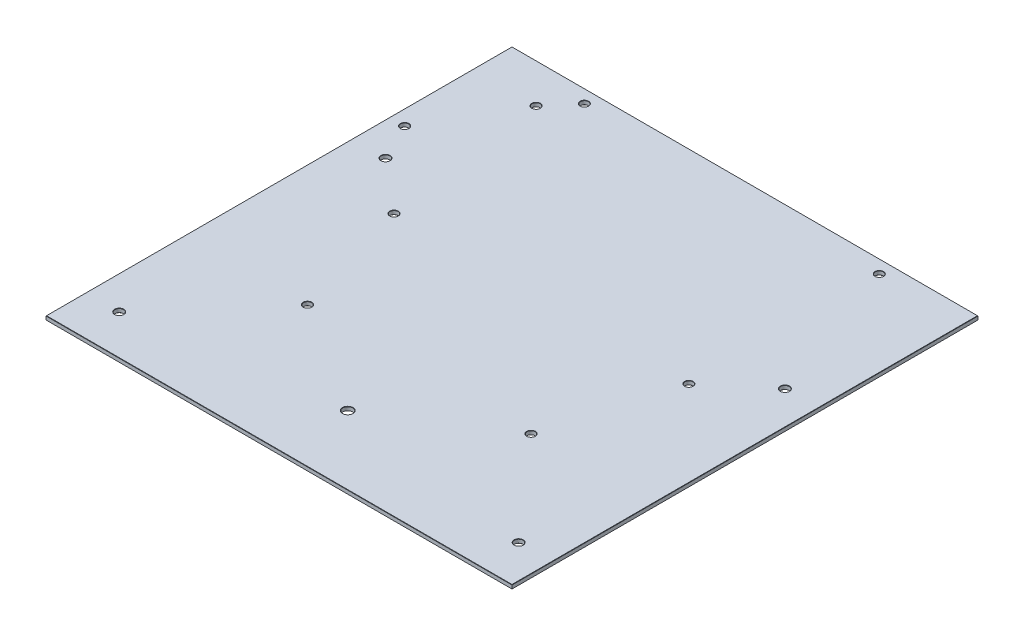
SolidWorks part; units mm, degrees
ref_plane "Front Plane" through (0, 0, 0) normal (0, 0, 1) x (1, 0, 0)
ref_plane "Top Plane" through (0, 0, 0) normal (0, 1, 0) x (1, 0, 0)
ref_plane "Right Plane" through (0, 0, 0) normal (1, 0, 0) x (0, 0, -1)
sketch "Sketch1" plane through (0, 0, 0) normal (0, 1, 0) x (1, 0, 0)
  line L1 (-175, 175) -> (175, 175)
  line L2 (-175, 175) -> (-175, -175)
  line L3 (-175, -175) -> (175, -175)
  line L4 (175, 175) -> (175, -175)
  line L5 (-175, 175) -> (175, -175) construction
  line L6 (-175, -175) -> (175, 175) construction
  point P0 (0, 0)
  dimension "D1" = 350
extrude "Boss-Extrude1" add sketch "Sketch1" along normal blind 3
sketch "Sketch6" plane through (0, 3, 0) normal (0, 1, 0) x (1, 0, 0)
  line L0 (-175, 55) -> (175, 55) construction
  line L1 (-175, 175) -> (-175, -175) construction
  line L2 (175, -175) -> (175, 175) construction
  line L3 (-150, -145) -> (-175, -145) construction
  line L4 (150, -145) -> (175, -145) construction
  line B0 (-150, -145) -> (150, -145) construction
  line B1 (150, -145) -> (150, 55) construction
  line B2 (150, 55) -> (-150, 55) construction
  line B3 (-150, 55) -> (-150, -145) construction
  line B4 (-150, -145) -> (150, 55) construction
  circle B5 centre (-150, -145) radius 3
  circle B6 centre (150, 55) radius 3
  circle B7 centre (150, -145) radius 3
  circle B8 centre (-150, 55) radius 3
sketch_block_instance "Block2-1"
sketch_block "Block2"
sketch "Sketch2" plane through (0, 3, 0) normal (0, 1, 0) x (1, 0, 0)
  line L0 (-175, 175) -> (-175, 55) construction
  line L1 (-175, 175) -> (-175, -175) construction
  line L2 (-175, 55) -> (175, 55) construction
  line L3 (175, -175) -> (175, 175) construction
  line L4 (-155, -175) -> (-155, -155) construction
  line L5 (-175, -175) -> (175, -175) construction
  line L6 (-155, -155) -> (155, -155) construction
  line L7 (155, -155) -> (155, -175) construction
  line L8 (-155, -155) -> (-155, -151.75) construction
  line L9 (155, -155) -> (155, -151.75) construction
  line L10 (155, -151.75) -> (-155, -151.75) construction
  line L11 (-151.75, 55) -> (-151.75, -151.75) construction
  line L12 (-151.75, -151.75) -> (151.75, 55) construction
  line L13 (151.75, 55) -> (151.75, -151.75) construction
  line L14 (151.75, -151.75) -> (-151.75, 55) construction
  line L15 (0, -48.375) -> (0, -123.375) construction
  circle A1 centre (-151.75, -151.75) radius 3.25 construction
  circle A2 centre (151.75, -151.75) radius 3.25 construction
  circle A3 centre (151.75, 55) radius 3.25 construction
  circle A4 centre (-151.75, 55) radius 3.25 construction
  circle A6 centre (0, -123.375) radius 3.75
  circle A7 centre (-150, 55) radius 3 construction
  circle A8 centre (150, 55) radius 3 construction
  circle A9 centre (150, -145) radius 3 construction
  circle A10 centre (-150, -145) radius 3 construction
  circle A11 centre (-150, 55) radius 3 construction
  circle A12 centre (150, 55) radius 3 construction
  circle A13 centre (150, -145) radius 3 construction
  circle A14 centre (-150, -145) radius 3 construction
  circle A15 centre (-150, -145) radius 3.25
  circle A16 centre (-150, 55) radius 3.25
  circle A17 centre (150, 55) radius 3.25
  circle A18 centre (150, -145) radius 3.25
  point P8 (-155, 55)
  point P9 (155, 55)
  dimension "D6" = 6.5
  dimension "D7" = 7.5
  dimension "D8" = 6.5
  dimension "D1" = 120
  dimension "D2" = 20
  dimension "D3" = 20
  dimension "D4" = 20
  dimension "D5" = 75
extrude "Cut-Extrude1" cut sketch "Sketch2" against normal up to surface (3 mm away) up to face at (0, 0, 0)
sketch "Sketch3" plane through (0, 3, 0) normal (0, 1, 0) x (1, 0, 0)
  circle A0 centre (-83.95, -69.6649) radius 3.05 construction
  circle A1 centre (83.95, -69.6649) radius 3.05 construction
  circle A2 centre (-83.95, -69.6649) radius 3.05
  circle A3 centre (83.95, -69.6649) radius 3.05
extrude "Cut-Extrude2" cut sketch "Sketch3" against normal up to surface (3 mm away) up to face at (150, 0, 148.25)
sketch "Sketch4" plane through (0, 3, 0) normal (0, 1, 0) x (1, 0, 0)
  circle A0 centre (-110.733, 165.1108) radius 3 construction
  circle A1 centre (-110.733, 165.1108) radius 3
  circle A2 centre (-110.75, 22.1108) radius 3 construction
  circle A3 centre (110.75, 22.0845) radius 3 construction
  circle A4 centre (110.767, 165.0845) radius 3 construction
  circle A5 centre (-110.75, 22.1108) radius 3
  circle A6 centre (110.75, 22.0845) radius 3
  circle A7 centre (110.767, 165.0845) radius 3
extrude "Cut-Extrude3" cut sketch "Sketch4" against normal up to surface (3 mm away) up to face at (-83.95, 0, 72.7149)
sketch "Sketch5" plane through (0, 3, 0) normal (0, 1, 0) x (1, 0, 0)
  circle A0 centre (-127.4584, 145.5807) radius 3.05 construction
  circle A1 centre (-163.7076, 83.0307) radius 3.05 construction
  circle A2 centre (-127.4584, 145.5807) radius 3.05
  circle A3 centre (-163.7076, 83.0307) radius 3.05
extrude "Cut-Extrude4" cut sketch "Sketch5" against normal up to surface (3 mm away) up to face at (110.767, 0, -162.0845)
chamfer "Chamfer1" distance 0.2 angle 45 34 edges at (0, 0, -175) (-175, 0, 0) (0, 0, 175) (175, 0, 0) (0, 0, 127.125) (83.95, 0, 72.7149) (-83.95, 0, 72.7149) (-110.733, 0, -162.1108) (-110.75, 0, -19.1108) (110.75, 0, -19.0845) (110.767, 0, -162.0845) (-163.7076, 0, -79.9807) (-127.4584, 0, -142.5307) (0, 3, 175) (-175, 3, 0) (0, 3, -175) (175, 3, 0) (0, 3, 127.125) (83.95, 3, 72.7149) (-83.95, 3, 72.7149) (-110.733, 3, -162.1108) (-110.75, 3, -19.1108) (110.75, 3, -19.0845) (110.767, 3, -162.0845) (-163.7076, 3, -79.9807) (-127.4584, 3, -142.5307) (-150, 0, 148.25) (-150, 0, -51.75) (150, 0, -51.75) (150, 0, 148.25) (-150, 3, 148.25) (-150, 3, -51.75) (150, 3, -51.75) (150, 3, 148.25)
